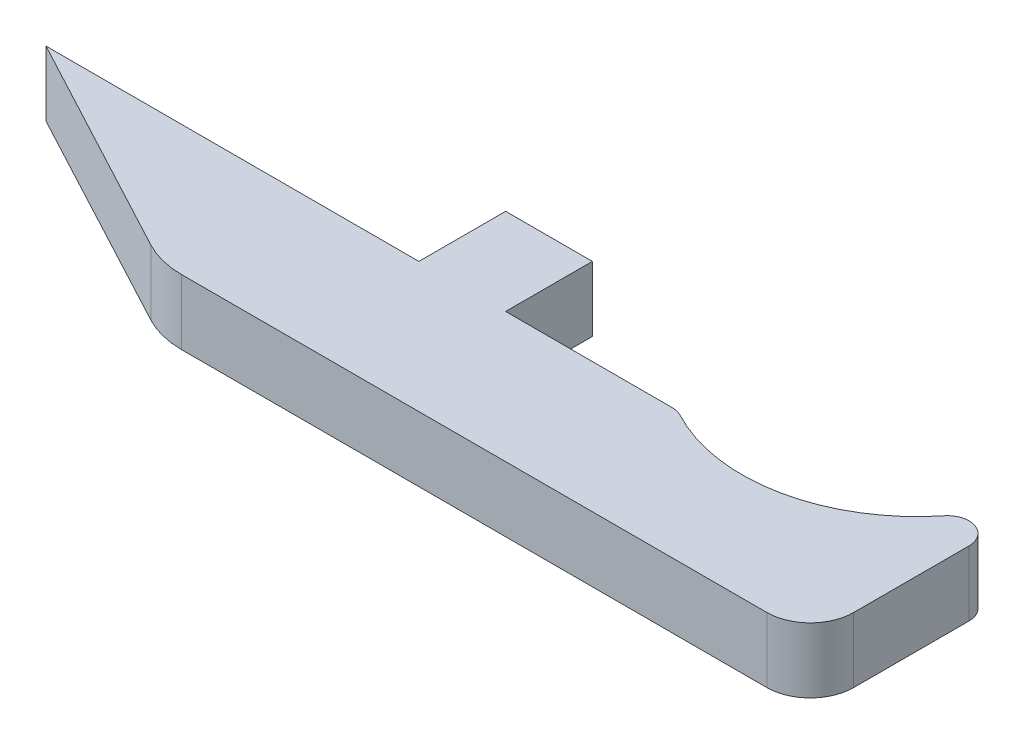
SolidWorks part; units mm, degrees
material "AISI 4130 Steel, annealed at 865C"
ref_plane "X-Y Datum" through (0, 0, 0) normal (0, 0, 1) x (1, 0, 0)
ref_plane "X-Z Datum" through (0, 0, 0) normal (0, 1, 0) x (1, 0, 0)
ref_plane "Y-Z Datum" through (0, 0, 0) normal (1, 0, 0) x (0, 0, -1)
sketch "Sketch1" plane through (0, 0, 0) normal (0, 1, 0) x (1, 0, 0)
  line L0 (58.9432, -32.213) -> (58.9432, -32.1941) construction
  line L1 (58.9432, -43.3287) -> (3.2156, -43.3287)
  line L2 (58.9432, -43.3287) -> (58.9432, -32.2035)
  line L3 (24.1452, -52.8537) -> (71.7702, -52.8537)
  line L4 (71.7702, -32.2035) -> (71.7702, -52.8537)
  line L5 (6.2845, -43.3287) -> (24.1452, -52.8537)
  line L8 (33.5895, -43.316) -> (3.1095, -43.316) construction
  line L9 (33.5895, -43.316) -> (3.1095, -43.316)
  circle A0 centre (58.9432, -32.2035) radius 12.827
  circle A1 centre (58.9432, -32.2035) radius 12.7
  circle A2 centre (58.9432, -32.2035) radius 12.7 construction
  dimension "D3" = 25.654
  dimension "D5" = 9.525
  dimension "D1" = 55.7276
  dimension "D2" = 11.1252
  dimension "D4" = 3.175
  dimension "D6" = 47.625
extrude "Boss-Extrude1" add sketch "Sketch1" along normal blind 4.7625 contours L1 A0 region at (43.8554, 0, 47.671)
fillet "Fillet1" radius 1.5875 2 edges at (52.5587, 2.3813, 43.3287) (71.7702, 2.3813, 32.2035)
fillet "Fillet2" radius 6.35 1 edges at (24.1452, 2.3813, 52.8537)
fillet "Fillet3" radius 3.175 1 edges at (71.7702, 2.3813, 52.8537)
sketch "Sketch2" plane through (0, 0, 43.3287) normal (0, 0, -1) x (-1, 0, 0)
  line L0 (-52.1488, 4.7625) -> (-6.2845, 4.7625) construction
  line L1 (-39.9395, 4.7625) -> (-33.5895, 4.7625)
  line L2 (-39.9395, 4.7625) -> (-39.9395, 0)
  line L3 (-39.9395, 0) -> (-33.5895, 0)
  line L4 (-33.5895, 4.7625) -> (-33.5895, 0)
  line L5 (-52.1488, 0) -> (-6.2845, 0) construction
  line L6 (-6.2845, 4.7625) -> (-6.2845, 0) construction
  dimension "D1" = 27.305
  dimension "D2" = 6.35
extrude "Boss-Extrude2" add sketch "Sketch2" along normal blind 6.35
